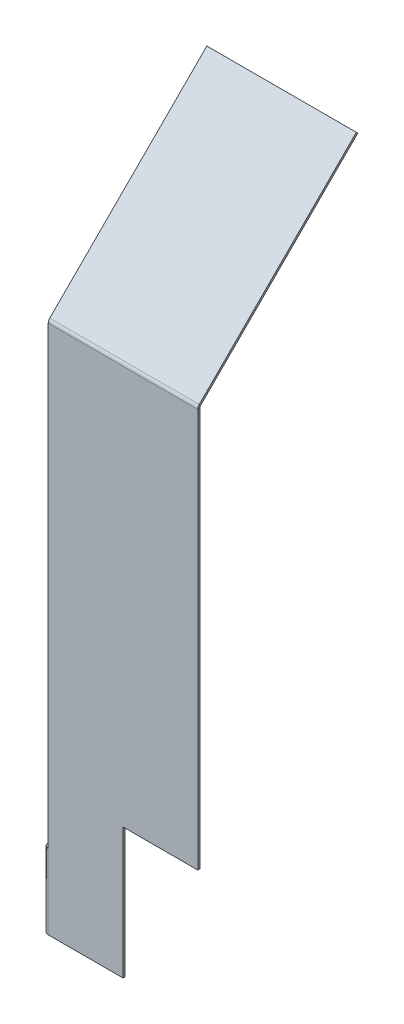
SolidWorks part; units mm, degrees
note: The reader was unsure of these and kept them because the rebuilt part matched: flange length of "Edge-Flange1", "Edge-Flange2".
ref_plane "Front Plane" through (0, 0, 0) normal (0, 0, 1) x (1, 0, 0)
ref_plane "Top Plane" through (0, 0, 0) normal (0, 1, 0) x (1, 0, 0)
ref_plane "Right Plane" through (0, 0, 0) normal (1, 0, 0) x (0, 0, -1)
sketch "Sketch1" plane through (0, 0, 0) normal (0, 0, 1) x (1, 0, 0)
  line L1 (-25.4, -110.15) -> (25.4, -110.15)
  line L2 (-25.4, -110.15) -> (-25.4, 69.85)
  line L3 (-25.4, 69.85) -> (25.4, 69.85)
  line L4 (25.4, -110.15) -> (25.4, 69.85)
  line L5 (-25.4, -110.15) -> (25.4, 69.85) construction
  line L6 (-25.4, 69.85) -> (25.4, -110.15) construction
  point P0 (0, 0)
  dimension "D1" = 50.8
  dimension "D2" = 180
base flange "Base-Flange1" sketch "Sketch1" thickness 0.7 reverse thickness direction no parameters "D1"=1
edge flange "Edge-Flange1" sketch "Sketch8" flange angle 90 flange length 25.4 flange position bend outside bend radius 1 thickness 0.7 relief rectangular parameters "D6"=0
sketch "Sketch8" plane through (-25.4, 0, -0.7) normal (-1, 0, 0) x (0, 1, 0)
  line L0 (69.85, 0) -> (-110.15, 0) construction
  line L1 (-84.75, 0) -> (-110.15, 0)
  line L2 (-110.15, 0) -> (-110.15, 24.7)
  line L3 (-110.15, 24.7) -> (-84.75, 24.7)
  line L5 (-84.75, 0) -> (-84.75, 24.7)
  dimension "D1" = 25.4
bend "EdgeBend1" bend radius 1 bend angle 90 parameters "D5"=1
sketch "Sketch9" plane through (0, 0, 0) normal (0, 0, 1) x (1, 0, 0)
  line L0 (-25.4, -84.75) -> (-25.4, -110.15) construction
  line L1 (25.4, -110.15) -> (0, -110.15)
  line L2 (25.4, -110.15) -> (25.4, -65.7)
  line L3 (25.4, -65.7) -> (0, -65.7)
  line L4 (0, -110.15) -> (0, -65.7)
  line L5 (25.4, -110.15) -> (25.4, 69.85) construction
  line L6 (-25.4, -110.15) -> (25.4, -110.15) construction
  dimension "D1" = 25.4
  dimension "D2" = 44.45
extrude "Cut-Extrude1" cut sketch "Sketch9" against normal blind 10 normal cut yes
edge flange "Edge-Flange2" sketch "Sketch17" flange angle 135 flange length 76.2 flange position bend outside bend radius 1 thickness 0.7 relief rectangular parameters "D6"=0
sketch "Sketch17" plane through (0, 69.85, -0.7) normal (0, 0.7071, 0.7071) x (1, 0, 0)
  line L0 (25.4, 0) -> (-25.4, 0) construction
  line L1 (25.4, 0) -> (-25.4, 0)
  line L2 (-25.4, 0) -> (-25.4, 75.9101)
  line L3 (-25.4, 75.9101) -> (25.4, 75.9101)
  line L4 (25.4, 75.9101) -> (25.4, 0)
bend "EdgeBend2" bend radius 1 bend angle 45 parameters "D5"=2
sketch "Bend-Lines1" [suppressed] plane through (0, 0, 0) normal (0, 1, 0) x (1, 0, 0)
sketch "Bounding-Box1" [suppressed] plane through (0, 0, 0) normal (0, 1, 0) x (1, 0, 0)
sheet metal parameters "Sheet-Metal1" thickness 0.7 parameters "D1"=1
flat pattern "Flat-Pattern1" [suppressed]
sketch "Bend-Lines2" plane through (0, 0, 0) normal (0, 1, 0) x (1, 0, 0)
sketch "Bounding-Box2" [suppressed] plane through (0, 0, 0) normal (0, 1, 0) x (1, 0, 0)
sheet metal parameters "Sheet-Metal2" thickness 0.7 parameters "D1"=1
flat pattern "Flat-Pattern1" [suppressed]
sketch "Bend-Lines2" plane through (0, 0, 0) normal (0, 1, 0) x (1, 0, 0)
sketch "Bounding-Box2" [suppressed] plane through (0, 0, 0) normal (0, 1, 0) x (1, 0, 0)
bend of the flat pattern "Flatten-<EdgeBend1>1"
sheet metal parameters "Sheet-Metal3" thickness 0.7 parameters "D1"=1
flat pattern "Flat-Pattern1" [suppressed]
sketch "Bend-Lines2" plane through (0, 0, 0) normal (0, 1, 0) x (1, 0, 0)
sketch "Bounding-Box2" [suppressed] plane through (0, 0, 0) normal (0, 1, 0) x (1, 0, 0)
bend of the flat pattern "Flatten-<EdgeBend1>1"
sheet metal parameters "Sheet-Metal5" thickness 0.7 parameters "D1"=1
flat pattern "Flat-Pattern1"
sketch "Bend-Lines2" plane through (0, 0, 0) normal (0, 0, 1) x (1, 0, 0)
  line L0 (25.4, 70.3801) -> (-25.4, 70.3801) construction
  line L1 (-26.4603, -109.2) -> (-26.4603, -134.6) construction
  line L2 (25.4, 70.3801) -> (-25.4, 70.3801) construction
  line L3 (-26.4603, -109.2) -> (-26.4603, -134.6) construction
sketch3d "Bounding-Box2" [suppressed]
  line L0 (19.501, -142.56, 0) -> (48.7802, 117.5746, 0) construction
  line L1 (-54.0437, -134.2822, 0) -> (-24.7645, 125.8523, 0) construction
  line L2 (19.501, -142.56, 0) -> (-54.0437, -134.2822, 0) construction
  line L3 (48.7802, 117.5746, 0) -> (-24.7645, 125.8523, 0) construction
bend of the flat pattern "Flatten-<EdgeBend1>1"
bend of the flat pattern "Flatten-<EdgeBend2>1"
